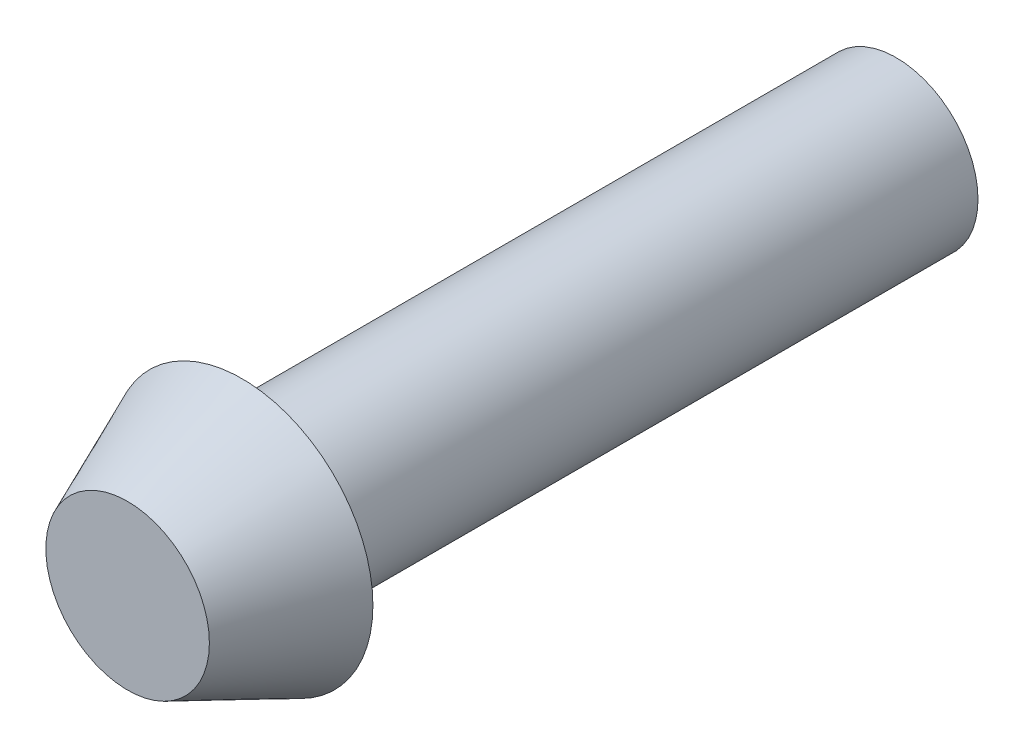
SolidWorks part; units mm, degrees
ref_plane "Front Plane" through (0, 0, 0) normal (0, 0, 1) x (1, 0, 0)
ref_plane "Top Plane" through (0, 0, 0) normal (0, 1, 0) x (1, 0, 0)
ref_plane "Right Plane" through (0, 0, 0) normal (1, 0, 0) x (0, 0, -1)
sketch "BaseBodySke" plane through (0, 0, 0) normal (0, 1, 0) x (1, 0, 0)
  line L0 (-5.08, 4.445) -> (-3.175, 4.445)
  line L1 (0, 0) -> (0, 54.1082) construction
  line L2 (0, 0) -> (0, 29.845)
  line L3 (0, 29.845) -> (-3.175, 29.845)
  line L4 (-3.175, 4.445) -> (-3.175, 29.845)
  line L5 (-5.08, 29.845) -> (-5.08, 4.445) construction
  line L6 (-5.08, 0) -> (-5.08, 4.445) construction
  line L7 (0, 0) -> (-3.175, 0)
  line L8 (-3.175, 0) -> (-5.08, 4.445)
  dimension "Diameter" = 6.35
  dimension "Head_Diameter" = 10.16
  dimension "Length" = 25.4
  dimension "Head_Depth" = 4.445
revolve "BaseBody" add sketch "BaseBodySke" angle 360 about L1
